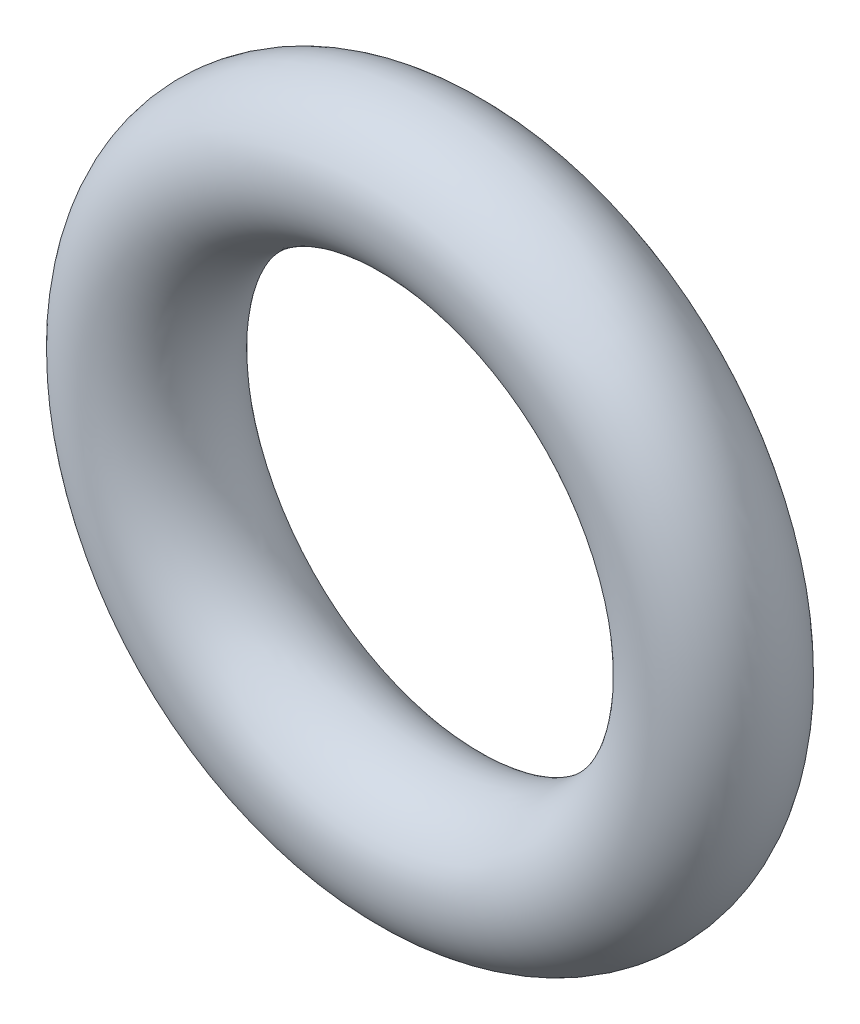
SolidWorks part; units mm, degrees
material "EPDM 60 Durometer"
ref_plane "Front Plane" through (0, 0, 0) normal (0, 0, 1) x (1, 0, 0)
ref_plane "Top Plane" through (0, 0, 0) normal (0, 1, 0) x (1, 0, 0)
ref_plane "Right Plane" through (0, 0, 0) normal (1, 0, 0) x (0, 0, -1)
sketch "Sketch1" plane through (0, 0, 0) normal (0, 0, 1) x (1, 0, 0)
  circle A0 centre (0, 0) radius 3
  dimension "D1" = 6
sweep "Sweep1" add path "Sketch1" circular profile diameter 1.5 parameters "D3"=1.5
